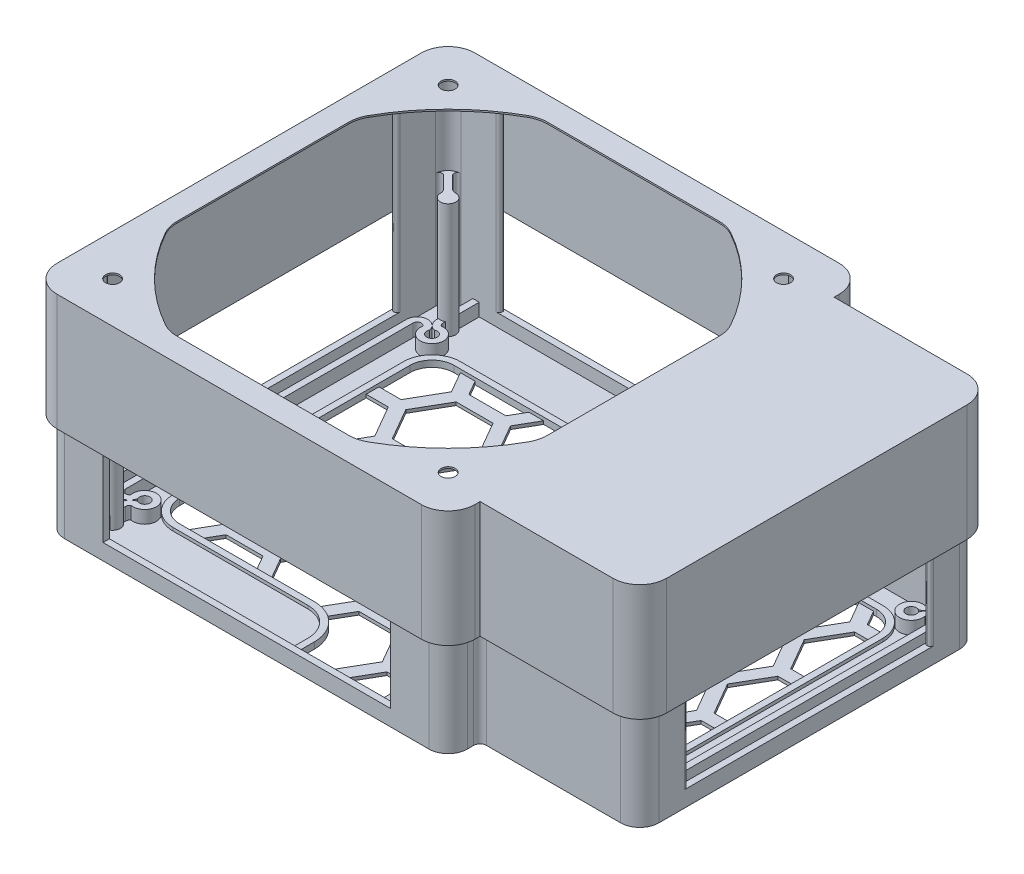
SolidWorks part; units mm, degrees
ref_plane "Front Plane" through (0, 0, 0) normal (0, 0, 1) x (1, 0, 0)
ref_plane "Top Plane" through (0, 0, 0) normal (0, 1, 0) x (1, 0, 0)
ref_plane "Right Plane" through (0, 0, 0) normal (1, 0, 0) x (0, 0, -1)
sketch "Sketch1" plane through (0, 0, 0) normal (0, 1, 0) x (1, 0, 0)
  line L0 (-80.9947, 45) -> (-80.9947, -45) construction
  line L1 (-85.9947, 57) -> (-85.9947, -57) construction
  line L2 (-85.9947, 0) -> (36.0053, 0) construction
  line L3 (0, 50) -> (0, -50) construction
  line L4 (80.9947, 45) -> (80.9947, -45) construction
  line L5 (-85.9947, 45) -> (-85.9947, -45) construction
  line L6 (85.9947, 47) -> (85.9947, -47) construction
  line L7 (32.0053, -61) -> (-81.9947, -61) construction
  line L8 (36.0053, -57) -> (36.0053, -55) construction
  line L9 (32.0053, 61) -> (-81.9947, 61) construction
  line L10 (40.0053, 51) -> (81.9947, 51) construction
  line L11 (40.0053, -51) -> (81.9947, -51) construction
  line L12 (85.9947, 45) -> (85.9947, -45) construction
  line L13 (36.0053, 55) -> (36.0053, 57) construction
  line L14 (40.0053, 53) -> (81.9947, 53)
  line L15 (87.9947, 47) -> (87.9947, -47)
  line L16 (40.0053, -53) -> (81.9947, -53)
  line L17 (38.0053, -57) -> (38.0053, -55)
  line L18 (32.0053, -63) -> (-81.9947, -63)
  line L19 (-87.9947, 57) -> (-87.9947, -57)
  line L20 (32.0053, 63) -> (-81.9947, 63)
  line L21 (38.0053, 55) -> (38.0053, 57)
  arc A0 (-78.5861, -45.6665) -> (-75.6694, -48.548) centre (-75.0053, -44.9589) cw construction
  arc A1 (-80.9947, -45) -> (-78.5861, -45.6665) centre (-79.6982, -45) ccw construction
  arc A2 (-74.9185, 51) -> (-75.6694, 48.5479) centre (-74.9185, 49.659) ccw construction
  arc A3 (-74.9185, -51) -> (-75.6694, -48.548) centre (-74.9185, -49.659) cw construction
  arc A4 (-80.9947, 45) -> (-78.5861, 45.6665) centre (-79.6982, 45) cw construction
  arc A5 (74.9185, -51) -> (75.6694, -48.548) centre (74.9185, -49.659) ccw construction
  arc A6 (-78.5861, 45.6665) -> (-75.6694, 48.5479) centre (-75.0053, 44.9589) ccw construction
  arc A7 (80.9947, -45) -> (78.5861, -45.6665) centre (79.6982, -45) cw construction
  arc A8 (78.5861, -45.6665) -> (75.6694, -48.548) centre (75.0053, -44.9589) ccw construction
  arc A9 (78.5861, 45.6665) -> (75.6693, 48.5479) centre (75.0053, 44.9589) cw construction
  arc A10 (80.9947, 45) -> (78.5861, 45.6665) centre (79.6982, 45) ccw construction
  arc A11 (74.9185, 51) -> (75.6693, 48.5479) centre (74.9185, 49.659) cw construction
  arc A12 (81.9947, -51) -> (85.9947, -47) centre (81.9947, -47) ccw construction
  arc A13 (85.9947, 47) -> (81.9947, 51) centre (81.9947, 47) ccw construction
  arc A14 (-85.9947, 57) -> (-81.9947, 61) centre (-81.9947, 57) cw construction
  arc A15 (-85.9947, -57) -> (-81.9947, -61) centre (-81.9947, -57) ccw construction
  arc A16 (36.0053, 57) -> (32.0053, 61) centre (32.0053, 57) ccw construction
  arc A17 (32.0053, -61) -> (36.0053, -57) centre (32.0053, -57) ccw construction
  arc A18 (40.0053, -51) -> (36.0053, -55) centre (40.0053, -55) ccw construction
  arc A19 (40.0053, 51) -> (36.0053, 55) centre (40.0053, 55) cw construction
  arc A20 (87.9947, 47) -> (81.9947, 53) centre (81.9947, 47) ccw
  arc A21 (81.9947, -53) -> (87.9947, -47) centre (81.9947, -47) ccw
  arc A22 (40.0053, -53) -> (38.0053, -55) centre (40.0053, -55) ccw
  arc A23 (32.0053, -63) -> (38.0053, -57) centre (32.0053, -57) ccw
  arc A24 (-87.9947, -57) -> (-81.9947, -63) centre (-81.9947, -57) ccw
  arc A25 (-87.9947, 57) -> (-81.9947, 63) centre (-81.9947, 57) cw
  arc A26 (38.0053, 57) -> (32.0053, 63) centre (32.0053, 57) ccw
  arc A27 (40.0053, 53) -> (38.0053, 55) centre (40.0053, 55) cw
  point P36 (-24.9947, 0)
  point P62 (36.0053, 51)
  dimension "D1" = 4
  dimension "D3" = 2
  dimension "D2" = 5
extrude "Boss-Extrude1" add sketch "Sketch1" against normal blind 1
sketch "Sketch2" plane through (0, 0, 0) normal (0, 1, 0) x (1, 0, 0)
  line L8 (81.9947, 53) -> (40.0053, 53)
  line L9 (81.9947, 53) -> (40.0053, 53)
  line L10 (87.9947, -47) -> (87.9947, 47)
  line L11 (87.9947, -47) -> (87.9947, 47)
  line L12 (40.0053, -53) -> (81.9947, -53)
  line L13 (40.0053, -53) -> (81.9947, -53)
  line L14 (38.0053, -57) -> (38.0053, -55)
  line L15 (38.0053, -57) -> (38.0053, -55)
  line L16 (-81.9947, -63) -> (32.0053, -63)
  line L17 (-81.9947, -63) -> (32.0053, -63)
  line L18 (-87.9947, 57) -> (-87.9947, -57)
  line L19 (-87.9947, 57) -> (-87.9947, -57)
  line L20 (32.0053, 63) -> (-81.9947, 63)
  line L21 (32.0053, 63) -> (-81.9947, 63)
  line L22 (38.0053, 55) -> (38.0053, 57)
  line L23 (38.0053, 55) -> (38.0053, 57)
  arc A8 (87.9947, 47) -> (81.9947, 53) centre (81.9947, 47) ccw
  arc A9 (87.9947, 47) -> (81.9947, 53) centre (81.9947, 47) ccw
  arc A10 (81.9947, -53) -> (87.9947, -47) centre (81.9947, -47) ccw
  arc A11 (81.9947, -53) -> (87.9947, -47) centre (81.9947, -47) ccw
  arc A12 (40.0053, -53) -> (38.0053, -55) centre (40.0053, -55) ccw
  arc A13 (40.0053, -53) -> (38.0053, -55) centre (40.0053, -55) ccw
  arc A14 (32.0053, -63) -> (38.0053, -57) centre (32.0053, -57) ccw
  arc A15 (32.0053, -63) -> (38.0053, -57) centre (32.0053, -57) ccw
  arc A16 (-87.9947, -57) -> (-81.9947, -63) centre (-81.9947, -57) ccw
  arc A17 (-87.9947, -57) -> (-81.9947, -63) centre (-81.9947, -57) ccw
  arc A18 (-81.9947, 63) -> (-87.9947, 57) centre (-81.9947, 57) ccw
  arc A19 (-81.9947, 63) -> (-87.9947, 57) centre (-81.9947, 57) ccw
  arc A20 (38.0053, 57) -> (32.0053, 63) centre (32.0053, 57) ccw
  arc A21 (38.0053, 57) -> (32.0053, 63) centre (32.0053, 57) ccw
  arc A22 (38.0053, 55) -> (40.0053, 53) centre (40.0053, 55) ccw
  arc A23 (38.0053, 55) -> (40.0053, 53) centre (40.0053, 55) ccw
  dimension "D1" = 0
extrude "Extrude-Thin1" add sketch "Sketch2" along normal blind 66 thin thin type one direction reverse wall 2
sketch "Sketch5" plane through (0, 0, 0) normal (0, 1, 0) x (1, 0, 0)
  line L0 (80.9947, 45) -> (80.9947, -45) construction
  line L1 (-80.9947, 45) -> (-80.9947, -45) construction
  line L2 (80.9947, 45) -> (80.9947, -45)
  line L3 (-80.9947, 45) -> (-80.9947, -45)
  line L4 (-76.2595, -49.659) -> (-76.2595, -61)
  line L5 (32.0053, -61) -> (-81.9947, -61) construction
  line L6 (-76.2595, 49.659) -> (-76.2595, 61)
  line L7 (32.0053, 61) -> (-81.9947, 61) construction
  arc A0 (75.6693, 48.5479) -> (74.9185, 51) centre (74.9185, 49.659) ccw construction
  arc A1 (75.6693, 48.5479) -> (78.5861, 45.6665) centre (75.0053, 44.9589) ccw construction
  arc A2 (80.9947, 45) -> (78.5861, 45.6665) centre (79.6982, 45) ccw construction
  arc A3 (78.5861, -45.6665) -> (80.9947, -45) centre (79.6982, -45) ccw construction
  arc A4 (78.5861, -45.6665) -> (75.6694, -48.548) centre (75.0053, -44.9589) ccw construction
  arc A5 (74.9185, -51) -> (75.6694, -48.548) centre (74.9185, -49.659) ccw construction
  arc A6 (-75.6694, -48.548) -> (-74.9185, -51) centre (-74.9185, -49.659) ccw construction
  arc A7 (-75.6694, -48.548) -> (-78.5861, -45.6665) centre (-75.0053, -44.9589) ccw construction
  arc A8 (-80.9947, -45) -> (-78.5861, -45.6665) centre (-79.6982, -45) ccw construction
  arc A9 (-74.9185, 51) -> (-75.6694, 48.5479) centre (-74.9185, 49.659) ccw construction
  arc A10 (-78.5861, 45.6665) -> (-75.6694, 48.5479) centre (-75.0053, 44.9589) ccw construction
  arc A11 (-78.5861, 45.6665) -> (-80.9947, 45) centre (-79.6982, 45) ccw construction
  arc A12 (75.6693, 48.5479) -> (74.9185, 51) centre (74.9185, 49.659) ccw
  arc A13 (75.6693, 48.5479) -> (78.5861, 45.6665) centre (75.0053, 44.9589) ccw
  arc A14 (80.9947, 45) -> (78.5861, 45.6665) centre (79.6982, 45) ccw
  arc A15 (78.5861, -45.6665) -> (80.9947, -45) centre (79.6982, -45) ccw
  arc A16 (78.5861, -45.6665) -> (75.6694, -48.548) centre (75.0053, -44.9589) ccw
  arc A17 (74.9185, -51) -> (75.6694, -48.548) centre (74.9185, -49.659) ccw
  arc A18 (-75.6694, -48.548) -> (-76.2595, -49.659) centre (-74.9185, -49.659) ccw
  arc A19 (-75.6694, -48.548) -> (-78.5861, -45.6665) centre (-75.0053, -44.9589) ccw
  arc A20 (-80.9947, -45) -> (-78.5861, -45.6665) centre (-79.6982, -45) ccw
  arc A21 (-76.2595, 49.659) -> (-75.6694, 48.5479) centre (-74.9185, 49.659) ccw
  arc A22 (-78.5861, 45.6665) -> (-75.6694, 48.5479) centre (-75.0053, 44.9589) ccw
  arc A23 (-78.5861, 45.6665) -> (-80.9947, 45) centre (-79.6982, 45) ccw
extrude "Extrude-Thin3" add sketch "Sketch5" along normal blind 4 thin contours A12 A13 A14 L2 A15 A16 A17 thin type one direction wall 2
extrude "Extrude-Thin4" add sketch "Sketch5<3>" along normal blind 4 thin contours L6 A21 A22 A23 L3 A20 A19 A18 L4 thin type one direction reverse wall 2
sketch "Sketch5<3>" plane through (0, 0, 0) normal (0, 1, 0) x (1, 0, 0) same geometry as "Sketch5"
sketch "Sketch6" plane through (0, 0, 0) normal (0, 1, 0) x (1, 0, 0)
  line L1 (-66.1053, 44.9589) -> (-23.9, 44.9589)
  line L2 (-75.0053, 36.0589) -> (-75.0053, -36.0589)
  line L3 (-66.1053, -44.9589) -> (-23.9, -44.9589)
  line L4 (75.0053, 36.0589) -> (75.0053, -36.0589)
  line L6 (-15, 50) -> (-15, -50)
  line L7 (-15, 61) -> (-15, 53.8589)
  line L8 (15, 50) -> (15, -50)
  line L9 (15, 61) -> (15, 53.8589)
  line L11 (23.9, 44.9589) -> (66.1053, 44.9589)
  line L12 (-15, -53.8589) -> (-15, -61)
  line L13 (15, -53.8589) -> (15, -61)
  line L14 (23.9, -44.9589) -> (66.1053, -44.9589)
  arc A0 (-75.0053, -36.0589) -> (-66.1053, -44.9589) centre (-66.1053, -36.0589) ccw
  arc A1 (66.1053, -44.9589) -> (75.0053, -36.0589) centre (66.1053, -36.0589) ccw
  arc A2 (66.1053, 44.9589) -> (75.0053, 36.0589) centre (66.1053, 36.0589) cw
  arc A3 (-66.1053, 44.9589) -> (-75.0053, 36.0589) centre (-66.1053, 36.0589) ccw
  arc A4 (15, -53.8589) -> (23.9, -44.9589) centre (23.9, -53.8589) cw
  arc A5 (-15, -53.8589) -> (-23.9, -44.9589) centre (-23.9, -53.8589) ccw
  arc A6 (23.9, 44.9589) -> (15, 53.8589) centre (23.9, 53.8589) cw
  arc A7 (-15, 53.8589) -> (-23.9, 44.9589) centre (-23.9, 53.8589) cw
  point P10 (75.0053, -44.9589)
  point P15 (-75.0053, 44.9589)
  point P30 (15, -44.9589)
  dimension "D1" = 8.9
  dimension "D4" = 8.9
  dimension "D2" = 15
  dimension "D3" = 15
extrude "Extrude-Thin5" add sketch "Sketch6" along normal blind 1 thin contours L12 A5 L3 A0 L2 A3 L1 A7 L7 thin type one direction reverse wall 2
extrude "Extrude-Thin6" add sketch "Sketch6<3>" along normal blind 1 thin contours L9 A6 L11 A2 L4 A1 L14 A4 L13 thin type one direction wall 2
sketch "Sketch6<3>" plane through (0, 0, 0) normal (0, 1, 0) x (1, 0, 0) same geometry as "Sketch6"
sketch "Sketch7" plane through (0, 0, 0) normal (0, 1, 0) x (1, 0, 0)
  line L10 (45.0973, 42.9589) -> (60.5874, 42.9589)
  line L11 (65.2062, 42.9589) -> (66.1053, 42.9589)
  line L12 (73.0053, 10.3736) -> (73.0053, -9.6264)
  line L13 (73.0053, -13.6264) -> (73.0053, -33.6264)
  line L14 (64.7747, -42.9589) -> (66.1053, -42.9589)
  line L15 (45.5287, -42.9589) -> (60.1559, -42.9589)
  line L16 (-37.6097, -42.9589) -> (-23.9, -42.9589)
  line L17 (-59.9329, -42.9589) -> (-42.2285, -42.9589)
  line L18 (-73.0053, -25.6264) -> (-73.0053, -36.0589)
  line L19 (-73.0053, -1.6264) -> (-73.0053, -21.6264)
  line L20 (-73.0053, 22.3736) -> (-73.0053, 2.3736)
  line L21 (-60.0053, 29.9589) -> (60.0053, 29.9589) construction
  line L22 (-60.0053, 29.9589) -> (-60.0053, -29.9589) construction
  line L23 (-60.0053, -29.9589) -> (60.0053, -29.9589) construction
  line L24 (-59.5015, 42.9589) -> (-42.6599, 42.9589)
  line L25 (-38.0411, 42.9589) -> (-23.9, 42.9589)
  line L26 (60.0053, 29.9589) -> (60.0053, -29.9589) construction
  line L27 (-66.1053, -42.9589) -> (-64.5517, -42.9589)
  line L29 (-13, -53.8589) -> (-13, -57.6264)
  line L31 (0.0877, -59) -> (13, -59)
  line L33 (13, -53.8589) -> (13, -59)
  line L34 (23.9, -42.9589) -> (40.9099, -42.9589)
  line L35 (73.0053, 34.3736) -> (73.0053, 14.3736)
  line L36 (23.9, 42.9589) -> (40.4785, 42.9589)
  line L37 (13, 59) -> (13, 53.8589)
  line L39 (0.5192, 59) -> (13, 59)
  line L40 (-13, 58.3736) -> (-13, 53.8589)
  line L41 (-66.1053, 42.9589) -> (-64.1203, 42.9589)
  line L42 (-73.0053, 36.0589) -> (-73.0053, 26.3736)
  line L71 (72.8249, -37.6264) -> (67.8534, -37.6264)
  line L72 (67.8534, -37.6264) -> (64.7747, -42.9589)
  line L95 (13.8553, -49.6264) -> (5.4996, -49.6264)
  line L96 (5.4996, -49.6264) -> (0.0877, -59)
  line L101 (37.8312, -37.6264) -> (26.2842, -37.6264)
  line L102 (26.2842, -37.6264) -> (23.1922, -42.9819)
  line L106 (40.9099, -42.9589) -> (37.8312, -37.6264)
  line L107 (58.6158, -25.6264) -> (47.0688, -25.6264)
  line L108 (47.0688, -25.6264) -> (41.2953, -35.6264)
  line L109 (41.2953, -35.6264) -> (45.5287, -42.9589)
  line L111 (60.1559, -42.9589) -> (64.3893, -35.6264)
  line L112 (64.3893, -35.6264) -> (58.6158, -25.6264)
  line L113 (73.0053, -13.6264) -> (67.8534, -13.6264)
  line L114 (67.8534, -13.6264) -> (62.0799, -23.6264)
  line L115 (62.0799, -23.6264) -> (67.8534, -33.6264)
  line L116 (67.8534, -33.6264) -> (73.0053, -33.6264)
  line L131 (-3.738, -37.6264) -> (-15.285, -37.6264)
  line L132 (-15.285, -37.6264) -> (-19.0275, -44.1085)
  line L134 (-13, -57.6264) -> (-3.738, -57.6264)
  line L135 (-3.738, -57.6264) -> (2.0355, -47.6264)
  line L136 (2.0355, -47.6264) -> (-3.738, -37.6264)
  line L137 (17.0466, -25.6264) -> (5.4996, -25.6264)
  line L138 (5.4996, -25.6264) -> (-0.2739, -35.6264)
  line L139 (-0.2739, -35.6264) -> (5.4996, -45.6264)
  line L140 (5.4996, -45.6264) -> (17.0466, -45.6264)
  line L141 (17.0466, -45.6264) -> (22.8201, -35.6264)
  line L142 (22.8201, -35.6264) -> (17.0466, -25.6264)
  line L143 (37.8312, -13.6264) -> (26.2842, -13.6264)
  line L144 (26.2842, -13.6264) -> (20.5107, -23.6264)
  line L145 (20.5107, -23.6264) -> (26.2842, -33.6264)
  line L146 (26.2842, -33.6264) -> (37.8312, -33.6264)
  line L147 (37.8312, -33.6264) -> (43.6047, -23.6264)
  line L148 (43.6047, -23.6264) -> (37.8312, -13.6264)
  line L149 (58.6158, -1.6264) -> (47.0688, -1.6264)
  line L150 (47.0688, -1.6264) -> (41.2953, -11.6264)
  line L151 (41.2953, -11.6264) -> (47.0688, -21.6264)
  line L152 (47.0688, -21.6264) -> (58.6158, -21.6264)
  line L153 (58.6158, -21.6264) -> (64.3893, -11.6264)
  line L154 (64.3893, -11.6264) -> (58.6158, -1.6264)
  line L155 (73.0053, 10.3736) -> (67.8534, 10.3736)
  line L156 (67.8534, 10.3736) -> (62.0799, 0.3736)
  line L157 (62.0799, 0.3736) -> (67.8534, -9.6264)
  line L158 (67.8534, -9.6264) -> (73.0053, -9.6264)
  line L161 (-45.3072, -37.6264) -> (-56.8542, -37.6264)
  line L162 (-56.8542, -37.6264) -> (-59.9329, -42.9589)
  line L166 (-42.2285, -42.9589) -> (-45.3072, -37.6264)
  line L167 (-24.5226, -25.6264) -> (-36.0696, -25.6264)
  line L168 (-36.0696, -25.6264) -> (-41.8431, -35.6264)
  line L169 (-41.8431, -35.6264) -> (-37.6097, -42.9589)
  line L171 (-23.0038, -42.9958) -> (-18.7491, -35.6264)
  line L172 (-18.7491, -35.6264) -> (-24.5226, -25.6264)
  line L173 (-3.738, -13.6264) -> (-15.285, -13.6264)
  line L174 (-15.285, -13.6264) -> (-21.0585, -23.6264)
  line L175 (-21.0585, -23.6264) -> (-15.285, -33.6264)
  line L176 (-15.285, -33.6264) -> (-3.738, -33.6264)
  line L177 (-3.738, -33.6264) -> (2.0355, -23.6264)
  line L178 (2.0355, -23.6264) -> (-3.738, -13.6264)
  line L179 (17.0466, -1.6264) -> (5.4996, -1.6264)
  line L180 (5.4996, -1.6264) -> (-0.2739, -11.6264)
  line L181 (-0.2739, -11.6264) -> (5.4996, -21.6264)
  line L182 (5.4996, -21.6264) -> (17.0466, -21.6264)
  line L183 (17.0466, -21.6264) -> (22.8201, -11.6264)
  line L184 (22.8201, -11.6264) -> (17.0466, -1.6264)
  line L185 (37.8312, 10.3736) -> (26.2842, 10.3736)
  line L186 (26.2842, 10.3736) -> (20.5107, 0.3736)
  line L187 (20.5107, 0.3736) -> (26.2842, -9.6264)
  line L188 (26.2842, -9.6264) -> (37.8312, -9.6264)
  line L189 (37.8312, -9.6264) -> (43.6047, 0.3736)
  line L190 (43.6047, 0.3736) -> (37.8312, 10.3736)
  line L191 (58.6158, 22.3736) -> (47.0688, 22.3736)
  line L192 (47.0688, 22.3736) -> (41.2953, 12.3736)
  line L193 (41.2953, 12.3736) -> (47.0688, 2.3736)
  line L194 (47.0688, 2.3736) -> (58.6158, 2.3736)
  line L195 (58.6158, 2.3736) -> (64.3893, 12.3736)
  line L196 (64.3893, 12.3736) -> (58.6158, 22.3736)
  line L197 (73.0053, 34.3736) -> (67.8534, 34.3736)
  line L198 (67.8534, 34.3736) -> (62.0799, 24.3736)
  line L199 (62.0799, 24.3736) -> (67.8534, 14.3736)
  line L200 (67.8534, 14.3736) -> (73.0053, 14.3736)
  line L203 (-45.3072, -13.6264) -> (-56.8542, -13.6264)
  line L204 (-56.8542, -13.6264) -> (-62.6277, -23.6264)
  line L205 (-62.6277, -23.6264) -> (-56.8542, -33.6264)
  line L206 (-56.8542, -33.6264) -> (-45.3072, -33.6264)
  line L207 (-45.3072, -33.6264) -> (-39.5337, -23.6264)
  line L208 (-39.5337, -23.6264) -> (-45.3072, -13.6264)
  line L209 (-24.5226, -1.6264) -> (-36.0696, -1.6264)
  line L210 (-36.0696, -1.6264) -> (-41.8431, -11.6264)
  line L211 (-41.8431, -11.6264) -> (-36.0696, -21.6264)
  line L212 (-36.0696, -21.6264) -> (-24.5226, -21.6264)
  line L213 (-24.5226, -21.6264) -> (-18.7491, -11.6264)
  line L214 (-18.7491, -11.6264) -> (-24.5226, -1.6264)
  line L215 (-3.738, 10.3736) -> (-15.285, 10.3736)
  line L216 (-15.285, 10.3736) -> (-21.0585, 0.3736)
  line L217 (-21.0585, 0.3736) -> (-15.285, -9.6264)
  line L218 (-15.285, -9.6264) -> (-3.738, -9.6264)
  line L219 (-3.738, -9.6264) -> (2.0355, 0.3736)
  line L220 (2.0355, 0.3736) -> (-3.738, 10.3736)
  line L221 (17.0466, 22.3736) -> (5.4996, 22.3736)
  line L222 (5.4996, 22.3736) -> (-0.2739, 12.3736)
  line L223 (-0.2739, 12.3736) -> (5.4996, 2.3736)
  line L224 (5.4996, 2.3736) -> (17.0466, 2.3736)
  line L225 (17.0466, 2.3736) -> (22.8201, 12.3736)
  line L226 (22.8201, 12.3736) -> (17.0466, 22.3736)
  line L227 (37.8312, 34.3736) -> (26.2842, 34.3736)
  line L228 (26.2842, 34.3736) -> (20.5107, 24.3736)
  line L229 (20.5107, 24.3736) -> (26.2842, 14.3736)
  line L230 (26.2842, 14.3736) -> (37.8312, 14.3736)
  line L231 (37.8312, 14.3736) -> (43.6047, 24.3736)
  line L232 (43.6047, 24.3736) -> (37.8312, 34.3736)
  line L234 (45.0973, 42.9589) -> (41.2953, 36.3736)
  line L235 (41.2953, 36.3736) -> (47.0688, 26.3736)
  line L236 (47.0688, 26.3736) -> (58.6158, 26.3736)
  line L237 (58.6158, 26.3736) -> (64.3893, 36.3736)
  line L238 (64.3893, 36.3736) -> (60.5874, 42.9589)
  line L241 (65.2062, 42.9589) -> (67.8534, 38.3736)
  line L242 (67.8534, 38.3736) -> (72.6055, 38.3736)
  line L245 (-45.3072, 10.3736) -> (-56.8542, 10.3736)
  line L246 (-56.8542, 10.3736) -> (-62.6277, 0.3736)
  line L247 (-62.6277, 0.3736) -> (-56.8542, -9.6264)
  line L248 (-56.8542, -9.6264) -> (-45.3072, -9.6264)
  line L249 (-45.3072, -9.6264) -> (-39.5337, 0.3736)
  line L250 (-39.5337, 0.3736) -> (-45.3072, 10.3736)
  line L251 (-24.5226, 22.3736) -> (-36.0696, 22.3736)
  line L252 (-36.0696, 22.3736) -> (-41.8431, 12.3736)
  line L253 (-41.8431, 12.3736) -> (-36.0696, 2.3736)
  line L254 (-36.0696, 2.3736) -> (-24.5226, 2.3736)
  line L255 (-24.5226, 2.3736) -> (-18.7491, 12.3736)
  line L256 (-18.7491, 12.3736) -> (-24.5226, 22.3736)
  line L257 (-3.738, 34.3736) -> (-15.285, 34.3736)
  line L258 (-15.285, 34.3736) -> (-21.0585, 24.3736)
  line L259 (-21.0585, 24.3736) -> (-15.285, 14.3736)
  line L260 (-15.285, 14.3736) -> (-3.738, 14.3736)
  line L261 (-3.738, 14.3736) -> (2.0355, 24.3736)
  line L262 (2.0355, 24.3736) -> (-3.738, 34.3736)
  line L263 (15.9765, 46.3736) -> (5.4996, 46.3736)
  line L264 (5.4996, 46.3736) -> (-0.2739, 36.3736)
  line L265 (-0.2739, 36.3736) -> (5.4996, 26.3736)
  line L266 (5.4996, 26.3736) -> (17.0466, 26.3736)
  line L267 (17.0466, 26.3736) -> (22.8201, 36.3736)
  line L268 (22.8201, 36.3736) -> (18.0262, 44.6769)
  line L271 (23.6351, 42.9621) -> (26.2842, 38.3736)
  line L272 (26.2842, 38.3736) -> (37.8312, 38.3736)
  line L273 (37.8312, 38.3736) -> (40.4785, 42.9589)
  line L287 (-45.3072, 34.3736) -> (-56.8542, 34.3736)
  line L288 (-56.8542, 34.3736) -> (-62.6277, 24.3736)
  line L289 (-62.6277, 24.3736) -> (-56.8542, 14.3736)
  line L290 (-56.8542, 14.3736) -> (-45.3072, 14.3736)
  line L291 (-45.3072, 14.3736) -> (-39.5337, 24.3736)
  line L292 (-39.5337, 24.3736) -> (-45.3072, 34.3736)
  line L294 (-38.0411, 42.9589) -> (-41.8431, 36.3736)
  line L295 (-41.8431, 36.3736) -> (-36.0696, 26.3736)
  line L296 (-36.0696, 26.3736) -> (-24.5226, 26.3736)
  line L297 (-24.5226, 26.3736) -> (-18.7491, 36.3736)
  line L298 (-18.7491, 36.3736) -> (-22.5963, 43.0371)
  line L299 (-3.738, 58.3736) -> (-13, 58.3736)
  line L301 (-18.6959, 44.2814) -> (-15.285, 38.3736)
  line L302 (-15.285, 38.3736) -> (-3.738, 38.3736)
  line L303 (-3.738, 38.3736) -> (2.0355, 48.3736)
  line L304 (2.0355, 48.3736) -> (-3.738, 58.3736)
  line L307 (0.5192, 59) -> (5.4996, 50.3736)
  line L308 (5.4996, 50.3736) -> (13.5722, 50.3736)
  line L331 (-59.5015, 42.9589) -> (-56.8542, 38.3736)
  line L332 (-56.8542, 38.3736) -> (-45.3072, 38.3736)
  line L333 (-45.3072, 38.3736) -> (-42.6599, 42.9589)
  line L389 (-66.0918, -25.6264) -> (-73.0053, -25.6264)
  line L393 (-64.5517, -42.9589) -> (-60.3183, -35.6264)
  line L394 (-60.3183, -35.6264) -> (-66.0918, -25.6264)
  line L395 (-66.0918, -1.6264) -> (-73.0053, -1.6264)
  line L398 (-73.0053, -21.6264) -> (-66.0918, -21.6264)
  line L399 (-66.0918, -21.6264) -> (-60.3183, -11.6264)
  line L400 (-60.3183, -11.6264) -> (-66.0918, -1.6264)
  line L401 (-66.0918, 22.3736) -> (-73.0053, 22.3736)
  line L404 (-73.0053, 2.3736) -> (-66.0918, 2.3736)
  line L405 (-66.0918, 2.3736) -> (-60.3183, 12.3736)
  line L406 (-60.3183, 12.3736) -> (-66.0918, 22.3736)
  line L410 (-73.0053, 26.3736) -> (-66.0918, 26.3736)
  line L411 (-66.0918, 26.3736) -> (-60.3183, 36.3736)
  line L412 (-60.3183, 36.3736) -> (-64.1203, 42.9589)
  arc A8 (15.9765, 46.3736) -> (18.0262, 44.6769) centre (23.9, 53.8589) ccw
  arc A9 (23.6351, 42.9621) -> (23.9, 42.9589) centre (23.9, 53.8589) ccw
  arc A10 (17.3034, -45.1816) -> (16.7561, -45.6264) centre (23.9, -53.8589) ccw
  arc A11 (13.8553, -49.6264) -> (13, -53.8589) centre (23.9, -53.8589) ccw
  arc A12 (-23.0038, -42.9958) -> (-23.9, -42.9589) centre (-23.9, -53.8589) ccw
  arc A14 (-73.0053, -36.0589) -> (-66.1053, -42.9589) centre (-66.1053, -36.0589) ccw construction
  arc A15 (-73.0053, -36.0589) -> (-66.1053, -42.9589) centre (-66.1053, -36.0589) ccw
  arc A16 (-13, -53.8589) -> (-19.0275, -44.1085) centre (-23.9, -53.8589) ccw
  arc A17 (-18.6959, 44.2814) -> (-13, 53.8589) centre (-23.9, 53.8589) ccw
  arc A18 (23.9, -42.9589) -> (23.1922, -42.9819) centre (23.9, -53.8589) ccw
  arc A19 (66.1053, -42.9589) -> (72.8249, -37.6264) centre (66.1053, -36.0589) ccw
  arc A20 (72.6055, 38.3736) -> (66.1053, 42.9589) centre (66.1053, 36.0589) ccw
  arc A21 (13, 53.8589) -> (13.5722, 50.3736) centre (23.9, 53.8589) ccw
  arc A22 (-23.9, 42.9589) -> (-22.5963, 43.0371) centre (-23.9, 53.8589) ccw
  arc A23 (-66.1053, 42.9589) -> (-73.0053, 36.0589) centre (-66.1053, 36.0589) ccw
extrude "Cut-Extrude1" cut sketch "Sketch7" against normal blind 1 contours A21 L37 L39 L307 L308 | A17 L301 L302 L303 L304 L299 L40 | A8 L263 L264 L265 L266 L267 L268 | A9 L271 L272 L273 L36 | L237 L238 L10 L234 L235 L236 | L242 A20 L11 L241 | L199 L200 L35 L197 L198 | L195 L196 L191 L192 L193 L194 | L231 L232 L227 L228 L229 L230 | L157 L158 L12 L155 L156 | L115 L116 L13 L113 L114 | L111 L112 L107 L108 L109 L15 | L153 L154 L149 L150 L151 L152 | L14 A19 L71 L72 | A18 L34 L106 L101 L102 | L147 L148 L143 L144 L145 L146 | L189 L190 L185 L186 L187 L188 | L225 L226 L221 L222 L223 L224 | L183 L184 L179 L180 L181 L182 | L219 L220 L215 L216 L217 L218 | L261 L262 L257 L258 L259 L260 | A22 L25 L294 L295 L296 L297 L298 | L332 L333 L24 L331 | L41 A23 L42 L410 L411 L412 | L291 L292 L287 L288 L289 L290 | L255 L256 L251 L252 L253 L254 | A10 L141 L142 L137 L138 L139 L140 | L177 L178 L173 L174 L175 L176 | L213 L214 L209 L210 L211 L212 | L249 L250 L245 L246 L247 L248 | L405 L406 L401 L20 L404 | L399 L400 L395 L19 L398 | L207 L208 L203 L204 L205 L206 | A12 L171 L172 L167 L168 L169 L16 | A16 L29 L134 L135 L136 L131 L132 | A11 L95 L96 L31 L33 | L17 L166 L161 L162 | L18 A15 L27 L393 L394 L389 region at (52.8423, 0, -35.1114) region at (68.8716, 0, -40.4684) region at (68.8132, 0, -0.3736) region at (68.8132, 0, 23.6264) region at (68.868, 0, 40.1171) region at (52.8423, 0, 34.661) region at (-30.2958, 0, 34.6613) region at (-51.0807, 0, 40.4797) region at (-67.5999, 0, 34.1993) region at (-67.9635, 0, 11.6264) region at (-67.9635, 0, -12.3736) region at (-51.0807, 0, -40.8088) region at (-30.2952, 0, -35.1124) region at (-8.0605, 0, 46.9647) region at (7.8444, 0, 54.6777) region at (32.0571, 0, 40.4799) region at (68.8132, 0, -24.3736) region at (32.0577, 0, -40.8088) region at (7.9412, 0, -55.0164) region at (-7.9384, 0, -47.7178) region at (-67.5562, 0, -34.6527) region at (11.272, 0, 35.6245) region at (32.0577, 0, 23.6264) region at (52.8423, 0, 11.6264) region at (-9.5115, 0, 23.6264) region at (11.2731, 0, 11.6264) region at (32.0577, 0, -0.3736) region at (52.8423, 0, -12.3736) region at (-51.0807, 0, 23.6264) region at (-30.2961, 0, 11.6264) region at (-9.5115, 0, -0.3736) region at (11.2731, 0, -12.3736) region at (32.0577, 0, -24.3736) region at (-51.0807, 0, -0.3736) region at (-30.2961, 0, -12.3736) region at (-9.5115, 0, -24.3736) region at (11.2556, 0, -36.345) region at (-51.0807, 0, -24.3736)
sketch "Sketch8" plane through (0, 66, 0) normal (0, 1, 0) x (1, 0, 0)
  line L16 (38.4053, 55) -> (38.4053, 57)
  line L17 (81.9947, 53.4) -> (40.0053, 53.4)
  line L18 (88.3947, -47) -> (88.3947, 47)
  line L19 (40.0053, -53.4) -> (81.9947, -53.4)
  line L20 (38.4053, -57) -> (38.4053, -55)
  line L21 (-81.9947, -63.4) -> (32.0053, -63.4)
  line L22 (-88.3947, 57) -> (-88.3947, -57)
  line L23 (32.0053, 63.4) -> (-81.9947, 63.4)
  line L24 (38.4053, 55) -> (38.4053, 57)
  line L25 (81.9947, 53.4) -> (40.0053, 53.4)
  line L26 (88.3947, -47) -> (88.3947, 47)
  line L27 (40.0053, -53.4) -> (81.9947, -53.4)
  line L28 (38.4053, -57) -> (38.4053, -55)
  line L29 (-81.9947, -63.4) -> (32.0053, -63.4)
  line L30 (-88.3947, 57) -> (-88.3947, -57)
  line L31 (32.0053, 63.4) -> (-81.9947, 63.4)
  arc A16 (38.4053, 57) -> (32.0053, 63.4) centre (32.0053, 57) ccw
  arc A17 (38.4053, 55) -> (40.0053, 53.4) centre (40.0053, 55) ccw
  arc A18 (88.3947, 47) -> (81.9947, 53.4) centre (81.9947, 47) ccw
  arc A19 (81.9947, -53.4) -> (88.3947, -47) centre (81.9947, -47) ccw
  arc A20 (40.0053, -53.4) -> (38.4053, -55) centre (40.0053, -55) ccw
  arc A21 (32.0053, -63.4) -> (38.4053, -57) centre (32.0053, -57) ccw
  arc A22 (-88.3947, -57) -> (-81.9947, -63.4) centre (-81.9947, -57) ccw
  arc A23 (-81.9947, 63.4) -> (-88.3947, 57) centre (-81.9947, 57) ccw
  arc A24 (38.4053, 57) -> (32.0053, 63.4) centre (32.0053, 57) ccw
  arc A25 (38.4053, 55) -> (40.0053, 53.4) centre (40.0053, 55) ccw
  arc A26 (88.3947, 47) -> (81.9947, 53.4) centre (81.9947, 47) ccw
  arc A27 (81.9947, -53.4) -> (88.3947, -47) centre (81.9947, -47) ccw
  arc A28 (40.0053, -53.4) -> (38.4053, -55) centre (40.0053, -55) ccw
  arc A29 (32.0053, -63.4) -> (38.4053, -57) centre (32.0053, -57) ccw
  arc A30 (-88.3947, -57) -> (-81.9947, -63.4) centre (-81.9947, -57) ccw
  arc A31 (-81.9947, 63.4) -> (-88.3947, 57) centre (-81.9947, 57) ccw
  dimension "D1" = 0.4
extrude "Extrude-Thin7" add sketch "Sketch8" against normal offset from surface (36 mm away) 30 separate body thin up to face at (-57.8484, 0, 0) thin type one direction wall 2
sketch "Sketch9" plane through (0, 66, 0) normal (0, 1, 0) x (1, 0, 0)
  line L0 (32.0053, -61) -> (-81.9947, -61) construction
  line L2 (-24.9947, -61) -> (-81.9947, -61) construction
  line L4 (-24.9947, 61) -> (-24.9947, -61) construction
  line L5 (-85.9947, 0) -> (36.0053, 0) construction
  line L6 (-51.8461, -58) -> (1.8567, -58)
  line L7 (-82.9947, -26.8515) -> (-82.9947, 26.8515)
  line L8 (32.0053, 65.4) -> (-81.9947, 65.4)
  line L9 (-90.3947, 57) -> (-90.3947, -57)
  line L10 (-81.9947, -65.4) -> (32.0053, -65.4)
  line L11 (40.4053, -57) -> (40.4053, -55.4)
  line L12 (40.4053, -55.4) -> (81.9947, -55.4)
  line L13 (90.3947, -47) -> (90.3947, 47)
  line L14 (81.9947, 55.4) -> (40.4053, 55.4)
  line L15 (40.4053, 55.4) -> (40.4053, 57)
  line L16 (-77.4947, -52.5) -> (27.5053, -52.5) construction
  line L17 (-90.3947, 57) -> (-90.3947, -57)
  line L18 (-81.9947, -65.4) -> (32.0053, -65.4)
  line L19 (40.4053, -57) -> (40.4053, -55.4)
  line L20 (40.4053, -55.4) -> (81.9947, -55.4)
  line L21 (90.3947, -47) -> (90.3947, 47)
  line L22 (81.9947, 55.4) -> (40.4053, 55.4)
  line L23 (40.4053, 55.4) -> (40.4053, 57)
  line L24 (-51.8462, 58) -> (1.8567, 58)
  line L25 (33.0053, -26.8515) -> (33.0053, 26.8515)
  line L26 (-77.4947, -52.5) -> (-77.4947, 52.5) construction
  line L27 (-77.4947, 52.5) -> (27.5053, 52.5) construction
  line L28 (27.5053, -52.5) -> (27.5053, 52.5) construction
  line L29 (-77.4947, -52.5) -> (27.5053, 52.5) construction
  line L30 (-77.4947, 52.5) -> (27.5053, -52.5) construction
  arc A0 (-56.7282, 56.7273) -> (-81.722, 31.7335) centre (-24.9947, 0) ccw
  arc A1 (-81.722, -31.7335) -> (-56.7282, -56.7273) centre (-24.9947, 0) ccw
  arc A2 (6.7388, -56.7273) -> (31.7325, -31.7336) centre (-24.9947, 0) ccw
  arc A3 (31.7325, 31.7336) -> (6.7388, 56.7273) centre (-24.9947, 0) ccw
  circle A4 centre (27.5053, 52.5) radius 2.2
  circle A5 centre (-77.4947, 52.5) radius 2.2
  arc A6 (40.4053, 57) -> (32.0053, 65.4) centre (32.0053, 57) ccw
  arc A7 (-81.9947, 65.4) -> (-90.3947, 57) centre (-81.9947, 57) ccw
  arc A8 (-90.3947, -57) -> (-81.9947, -65.4) centre (-81.9947, -57) ccw
  arc A9 (32.0053, -65.4) -> (40.4053, -57) centre (32.0053, -57) ccw
  arc A10 (81.9947, -55.4) -> (90.3947, -47) centre (81.9947, -47) ccw
  arc A11 (90.3947, 47) -> (81.9947, 55.4) centre (81.9947, 47) ccw
  arc A12 (40.4053, 57) -> (32.0053, 65.4) centre (32.0053, 57) ccw
  arc A13 (-81.9947, 65.4) -> (-90.3947, 57) centre (-81.9947, 57) ccw
  arc A14 (-90.3947, -57) -> (-81.9947, -65.4) centre (-81.9947, -57) ccw
  arc A15 (32.0053, -65.4) -> (40.4053, -57) centre (32.0053, -57) ccw
  arc A16 (81.9947, -55.4) -> (90.3947, -47) centre (81.9947, -47) ccw
  arc A17 (90.3947, 47) -> (81.9947, 55.4) centre (81.9947, 47) ccw
  circle A18 centre (27.5053, -52.5) radius 2.2
  circle A19 centre (-77.4947, -52.5) radius 2.2
  arc A20 (-81.722, -31.7335) -> (-82.9947, -26.8515) centre (-72.9947, -26.8515) cw
  arc A21 (-51.8461, -58) -> (-56.7282, -56.7273) centre (-51.8461, -48) cw
  arc A22 (6.7388, -56.7273) -> (1.8567, -58) centre (1.8567, -48) cw
  arc A23 (33.0053, -26.8515) -> (31.7325, -31.7336) centre (23.0053, -26.8515) cw
  arc A24 (31.7325, 31.7336) -> (33.0053, 26.8515) centre (23.0053, 26.8515) cw
  arc A25 (1.8567, 58) -> (6.7388, 56.7273) centre (1.8567, 48) cw
  arc A26 (-56.7282, 56.7273) -> (-51.8462, 58) centre (-51.8462, 48) cw
  arc A27 (-82.9947, 26.8515) -> (-81.722, 31.7335) centre (-72.9947, 26.8515) cw
  point P26 (-24.9947, 0)
  arc M18 (32.0053, 63.4) -> (38.4053, 57) centre (32.0053, 57) cw
  line M19 (38.4053, 57) -> (38.4053, 55)
  arc M20 (38.4053, 55) -> (40.0053, 53.4) centre (40.0053, 55) ccw
  line M21 (40.0053, 53.4) -> (81.9947, 53.4)
  arc M22 (81.9947, 53.4) -> (88.3947, 47) centre (81.9947, 47) cw
  line M23 (88.3947, 47) -> (88.3947, -47)
  arc M24 (88.3947, -47) -> (81.9947, -53.4) centre (81.9947, -47) cw
  line M25 (81.9947, -53.4) -> (40.0053, -53.4)
  arc M26 (40.0053, -53.4) -> (38.4053, -55) centre (40.0053, -55) ccw
  line M27 (38.4053, -55) -> (38.4053, -57)
  arc M28 (38.4053, -57) -> (32.0053, -63.4) centre (32.0053, -57) cw
  line M29 (32.0053, -63.4) -> (-81.9947, -63.4)
  arc M30 (-81.9947, -63.4) -> (-88.3947, -57) centre (-81.9947, -57) cw
  line M31 (-88.3947, -57) -> (-88.3947, 57)
  arc M32 (-88.3947, 57) -> (-81.9947, 63.4) centre (-81.9947, 57) cw
  line M33 (-81.9947, 63.4) -> (32.0053, 63.4)
  arc M34 (40.4053, 57) -> (32.0053, 65.4) centre (32.0053, 57) ccw
  line M35 (32.0053, 65.4) -> (-81.9947, 65.4)
  arc M36 (-81.9947, 65.4) -> (-90.3947, 57) centre (-81.9947, 57) ccw
  line M37 (-90.3947, 57) -> (-90.3947, -57)
  arc M38 (-90.3947, -57) -> (-81.9947, -65.4) centre (-81.9947, -57) ccw
  line M39 (-81.9947, -65.4) -> (32.0053, -65.4)
  arc M40 (32.0053, -65.4) -> (40.4053, -57) centre (32.0053, -57) ccw
  line M41 (40.4053, -57) -> (40.4053, -55.4)
  line M42 (40.4053, -55.4) -> (81.9947, -55.4)
  arc M43 (81.9947, -55.4) -> (90.3947, -47) centre (81.9947, -47) ccw
  line M44 (90.3947, -47) -> (90.3947, 47)
  arc M45 (90.3947, 47) -> (81.9947, 55.4) centre (81.9947, 47) ccw
  line M46 (81.9947, 55.4) -> (40.4053, 55.4)
  line M47 (40.4053, 55.4) -> (40.4053, 57)
  dimension "D2" = 10
  dimension "D1" = 0
extrude "Boss-Extrude2" add sketch "Sketch9" along normal blind 0.5 contours M47 M34 M35 M36 M37 M38 M39 M40 M41 M42 M43 M44 M45 M46 M33 M18 M19 M20 M21 M22 M23 M24 M25 M26 M27 M28 M29 M30 M31 M32 | A19 A18 A5 A4 L7 A27 A0 A26 L24 A25 A3 A24 L25 A23 A2 A22 L6 A21 A1 A20 M18 M33 M32 M31 M30 M29 M28 M27 M26 M25 M24 M23 M22 M21 M20 M19 region at (37.7872, 66, -62.7819) region at (34.9924, 66, -59.9871)
sketch "Sketch10" plane through (0, 66, 0) normal (0, 1, 0) x (1, 0, 0)
  line L0 (-87.9947, 0) -> (-87.9947, 45) construction
  line L1 (-87.9947, 57) -> (-87.9947, -57) construction
  line L2 (-81.9947, 61) -> (-69.9947, 61) construction
  line L3 (-84.1984, -45) -> (-91.791, -45)
  line L4 (-84.1984, -45) -> (-84.1984, 45)
  line L5 (-84.1984, 45) -> (-91.791, 45)
  line L6 (-91.791, -45) -> (-91.791, 45)
  line L7 (-84.1984, -45) -> (-91.791, 45) construction
  line L8 (-84.1984, 45) -> (-91.791, -45) construction
  line L9 (32.0053, 61) -> (-81.9947, 61) construction
  line L10 (87.9947, 47) -> (87.9947, -47) construction
  line L11 (32.0053, 61) -> (20.0053, 61) construction
  line L12 (20.0053, 57.0282) -> (-69.9947, 57.0282)
  line L13 (20.0053, 57.0282) -> (20.0053, 64.9718)
  line L14 (20.0053, 64.9718) -> (-69.9947, 64.9718)
  line L15 (-69.9947, 57.0282) -> (-69.9947, 64.9718)
  line L16 (20.0053, 57.0282) -> (-69.9947, 64.9718) construction
  line L17 (20.0053, 64.9718) -> (-69.9947, 57.0282) construction
  line L18 (81.1796, -38) -> (94.8098, -38)
  line L19 (81.1796, -38) -> (81.1796, 38)
  line L20 (81.1796, 38) -> (94.8098, 38)
  line L21 (94.8098, -38) -> (94.8098, 38)
  line L22 (81.1796, -38) -> (94.8098, 38) construction
  line L23 (81.1796, 38) -> (94.8098, -38) construction
  line L24 (0, 0) -> (-27.3822, 0) construction
  line L25 (20.0053, -64.9718) -> (-69.9947, -57.0282) construction
  line L26 (20.0053, -57.0282) -> (-69.9947, -64.9718) construction
  line L27 (-69.9947, -57.0282) -> (-69.9947, -64.9718)
  line L28 (20.0053, -64.9718) -> (-69.9947, -64.9718)
  line L29 (20.0053, -57.0282) -> (20.0053, -64.9718)
  line L30 (20.0053, -57.0282) -> (-69.9947, -57.0282)
  point P13 (-24.9947, 61)
  point P18 (87.9947, 0)
  point P35 (-24.9947, -61)
extrude "Cut-Extrude2" cut sketch "Sketch10" against normal up to surface (62 mm away) up to face at (-77.3808, 4, 0)
fillet "Fillet1" radius 1 12 edges at (-87.9947, 35, 45) (-85.9947, 35, 45) (85.9947, 35, 38) (87.9947, 35, 38) (87.9947, 35, -38) (85.9947, 35, -38) (20.0053, 35, -63) (20.0053, 35, -61) (-69.9947, 35, -63) (-69.9947, 35, -61) (-85.9947, 35, -45) (-87.9947, 35, -45)
sketch "Sketch12" plane through (0, 0, 0) normal (0, 1, 0) x (1, 0, 0)
  line L0 (-84.8231, 59.8284) -> (-77.4947, 52.5) construction
  line L1 (-85.5302, 59.1213) -> (-80.5385, 54.1296)
  line L2 (-84.116, 60.5355) -> (-79.1243, 55.5438)
  line L3 (-24.9947, 63) -> (-24.9947, 76.1039) construction
  line L5 (-84.8231, 59.8284) -> (-84.8231, 61.7284) construction
  line L6 (34.8337, 59.8284) -> (34.8337, 61.7284) construction
  line L8 (-85.9947, 0) -> (36.0053, 0) construction
  line L9 (34.8337, 59.8284) -> (27.5053, 52.5) construction
  line L10 (34.1266, 60.5355) -> (29.1349, 55.5438)
  line L11 (35.5408, 59.1213) -> (30.5491, 54.1296)
  line L12 (34.8337, -59.8284) -> (27.5053, -52.5) construction
  line L13 (34.8337, -59.8284) -> (34.8337, -61.7284) construction
  line L14 (-84.8231, -59.8284) -> (-84.8231, -61.7284) construction
  line L15 (-24.9947, -63) -> (-24.9947, -76.1039) construction
  line L16 (-84.8231, -59.8284) -> (-77.4947, -52.5) construction
  line L17 (35.5408, -59.1213) -> (30.5491, -54.1296)
  line L18 (34.1266, -60.5355) -> (29.1349, -55.5438)
  line L19 (-84.116, -60.5355) -> (-79.1243, -55.5438)
  line L20 (-85.5302, -59.1213) -> (-80.5385, -54.1296)
  arc A1 (-79.8944, 52.5386) -> (-77.5333, 54.8997) centre (-77.4947, 52.5) ccw
  arc A2 (-85.5302, 59.1213) -> (-84.116, 60.5355) centre (-84.8231, 59.8284) cw
  circle A4 centre (-77.4947, 52.5) radius 2.2 construction
  circle A5 centre (-77.4947, 52.5) radius 1.4 construction
  circle A6 centre (27.5053, 52.5) radius 1.4 construction
  arc A7 (-77.5333, 54.8997) -> (-79.1243, 55.5438) centre (-77.5686, 57.0994) cw
  arc A8 (-79.8944, 52.5386) -> (-80.5385, 54.1296) centre (-82.0941, 52.5739) ccw
  circle A9 centre (27.5053, 52.5) radius 2.2 construction
  arc A10 (29.905, 52.5386) -> (30.5491, 54.1296) centre (32.1047, 52.5739) cw
  arc A11 (27.5439, 54.8997) -> (29.1349, 55.5438) centre (27.5792, 57.0994) ccw
  arc A12 (35.5408, 59.1213) -> (34.1266, 60.5355) centre (34.8337, 59.8284) ccw
  arc A13 (29.905, 52.5386) -> (27.5439, 54.8997) centre (27.5053, 52.5) cw
  circle A14 centre (27.5053, -52.5) radius 2.2 construction
  circle A15 centre (27.5053, -52.5) radius 1.4 construction
  circle A16 centre (-77.4947, -52.5) radius 1.4 construction
  circle A17 centre (-77.4947, -52.5) radius 2.2 construction
  arc A18 (29.905, -52.5386) -> (27.5439, -54.8997) centre (27.5053, -52.5) ccw
  arc A19 (35.5408, -59.1213) -> (34.1266, -60.5355) centre (34.8337, -59.8284) cw
  arc A20 (27.5439, -54.8997) -> (29.1349, -55.5438) centre (27.5792, -57.0994) cw
  arc A21 (29.905, -52.5386) -> (30.5491, -54.1296) centre (32.1047, -52.5739) ccw
  arc A22 (-79.8944, -52.5386) -> (-80.5385, -54.1296) centre (-82.0941, -52.5739) cw
  arc A23 (-77.5333, -54.8997) -> (-79.1243, -55.5438) centre (-77.5686, -57.0994) ccw
  arc A24 (-85.5302, -59.1213) -> (-84.116, -60.5355) centre (-84.8231, -59.8284) ccw
  arc A25 (-79.8944, -52.5386) -> (-77.5333, -54.8997) centre (-77.4947, -52.5) cw
extrude "Boss-Extrude3" add sketch "Sketch12" along normal offset from surface (36 mm away) 30 up to face at (-81.2604, 66, -56.2657)
fillet "Fillet2" radius 1 8 edges at (35.451, 18, -59.0315) (34.0368, 18, -60.4457) (35.451, 18, 59.0315) (34.0368, 18, 60.4457) (-85.4404, 18, 59.0315) (-84.0262, 18, 60.4457) (-84.0262, 18, -60.4457) (-85.4404, 18, -59.0315)
